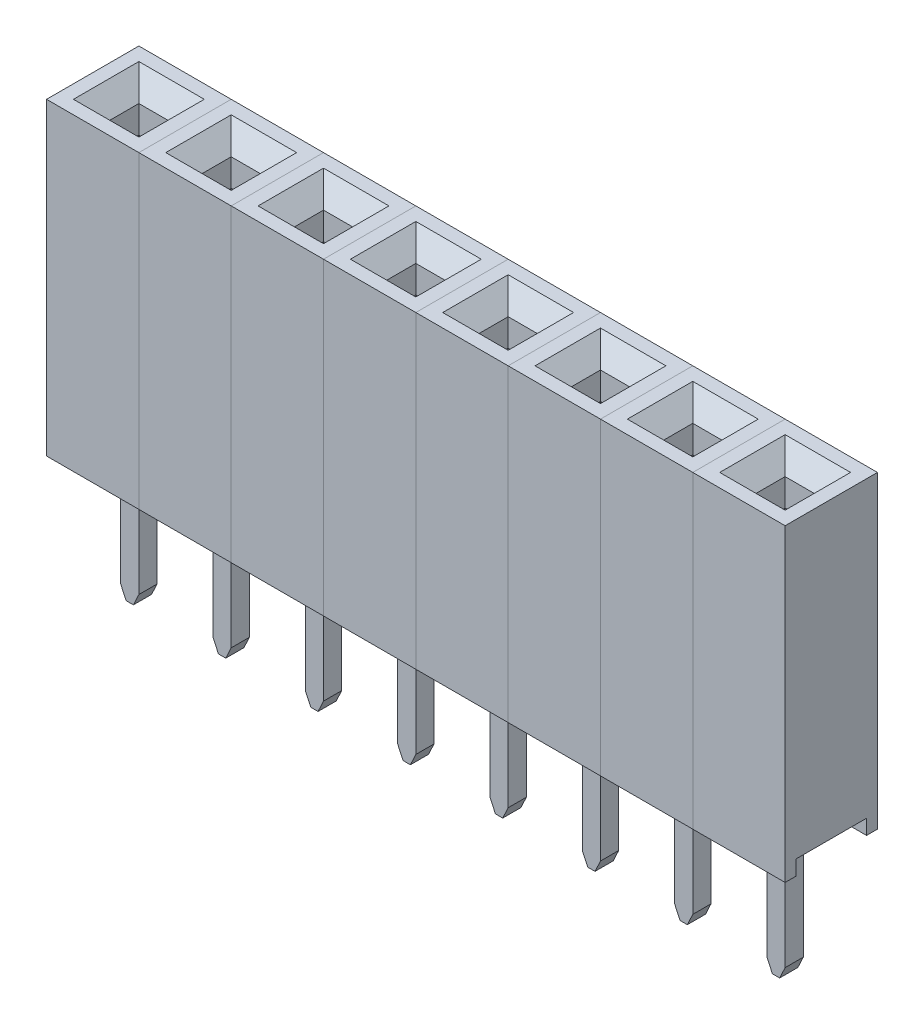
SolidWorks part; units mm, degrees
ref_plane "Front" through (0, 0, 0) normal (0, 0, 1) x (1, 0, 0)
ref_plane "Top" through (0, 0, 0) normal (0, 1, 0) x (1, 0, 0)
ref_plane "Right" through (0, 0, 0) normal (1, 0, 0) x (0, 0, -1)
sketch "Sketch1" plane through (0, 0, 0) normal (0, 0, 1) x (1, 0, 0)
  line L1 (1.27, -4.25) -> (-1.27, -4.25)
  line L2 (1.27, -4.25) -> (1.27, 4.25)
  line L3 (1.27, 4.25) -> (-1.27, 4.25)
  line L4 (-1.27, -4.25) -> (-1.27, 4.25)
  line L5 (1.27, -4.25) -> (-1.27, 4.25) construction
  line L6 (1.27, 4.25) -> (-1.27, -4.25) construction
  point P0 (0, 0)
  dimension "D1" = 2.54
  dimension "D2" = 8.5
extrude "Boss-Extrude1" add sketch "Sketch1" along normal mid plane 2.54
sketch "Sketch2" plane through (0, 0, 0) normal (1, 0, 0) x (0, 0, -1)
  line L0 (-0.97, -4.25) -> (0.97, -4.25)
  line L1 (-1.27, -4.25) -> (1.27, -4.25) construction
  line L2 (0.97, -4.25) -> (0.97, -3.8396)
  line L3 (0.97, -3.8396) -> (-0.97, -3.8396)
  line L4 (-0.97, -3.8396) -> (-0.97, -4.25)
  line L5 (1.27, -4.25) -> (1.27, 4.25) construction
  line L6 (-1.27, -4.25) -> (-1.27, 4.25) construction
  dimension "D1" = 0.3
  dimension "D2" = 0.3
extrude "Cut-Extrude1" cut sketch "Sketch2" against normal mid plane 100
sketch "Sketch4" plane through (0, 4.25, 0) normal (0, 1, 0) x (1, 0, 0)
  line L0 (-1.27, 0) -> (1.27, 0) construction
  line L1 (-1.27, -1.27) -> (-1.27, 1.27) construction
  line L2 (1.27, -1.27) -> (1.27, 1.27) construction
  line L4 (-0.875, 0.875) -> (0.875, 0.875)
  line L5 (-0.875, 0.875) -> (-0.875, -0.875)
  line L6 (-0.875, -0.875) -> (0.875, -0.875)
  line L7 (0.875, 0.875) -> (0.875, -0.875)
  line L8 (-0.875, 0.875) -> (0.875, -0.875) construction
  line L9 (-0.875, -0.875) -> (0.875, 0.875) construction
  line L10 (-0.4, 0.4) -> (0.4, 0.4)
  line L11 (-0.4, 0.4) -> (-0.4, -0.4)
  line L12 (-0.4, -0.4) -> (0.4, -0.4)
  line L13 (0.4, 0.4) -> (0.4, -0.4)
  line L14 (-0.4, 0.4) -> (0.4, -0.4) construction
  line L15 (-0.4, -0.4) -> (0.4, 0.4) construction
  point P6 (0, 0)
  point P11 (0, 0)
  point P16 (0, 0)
  dimension "D1" = 1.75
  dimension "D2" = 0.8
extrude "Cut-Extrude2" cut sketch "Sketch4" against normal blind 1.5 contours L13 L10 L11 L12 region at (0, 4.25, 0)
chamfer "Chamfer1" distance 0.5 angle 45 4 edges at (0, 4.25, -0.4) (-0.4, 4.25, 0) (0, 4.25, 0.4) (0.4, 4.25, 0)
sketch "Sketch5" plane through (0, 0, 0) normal (0, 1, 0) x (1, 0, 0)
  line L1 (-0.9, 0.9) -> (0.9, 0.9)
  line L2 (-0.9, 0.9) -> (-0.9, -0.9)
  line L3 (-0.9, -0.9) -> (0.9, -0.9)
  line L4 (0.9, 0.9) -> (0.9, -0.9)
extrude "Cut-Extrude3" cut sketch "Sketch5" against normal blind 3 and the other way blind 3
sketch "Sketch9" plane through (0, 0, 0) normal (0, 0, 1) x (1, 0, 0)
  line L0 (0, 1.6008) -> (0, -6.2684) construction
  line L1 (0.8528, -1.3416) -> (0.6022, -1.2609)
  line L2 (0.6022, -1.2609) -> (0.4133, 1.4919)
  line L3 (0.2803, 1.3393) -> (0.5075, -1.9717)
  line L4 (0.8528, -1.3416) -> (0.8528, -2.6933)
  line L5 (0.8528, -2.6933) -> (0.2807, -3.0533)
  line L6 (0.2807, -3.0533) -> (-0.2807, -3.0533)
  line L7 (-0.8528, -2.6933) -> (-0.2807, -3.0533)
  line L8 (-0.8528, -1.3416) -> (-0.8528, -2.6933)
  line L9 (-0.8528, -1.3416) -> (-0.6022, -1.2609)
  line L10 (-0.6022, -1.2609) -> (-0.4133, 1.4919)
  line L11 (-0.2803, 1.3393) -> (-0.5075, -1.9717)
  line L12 (-0.1, -7.6212) -> (0.1, -7.6212)
  line L13 (0.1, -7.6212) -> (0.25, -7.2995)
  line L14 (0.25, -7.2995) -> (0.25, -3.0533)
  line L15 (-0.1, -7.6212) -> (-0.25, -7.2995)
  line L16 (-0.25, -7.2995) -> (-0.25, -3.0533)
  line L19 (0, 0) -> (0, -10.2857) construction
  arc A0 (0.4133, 1.4919) -> (0.2803, 1.3393) centre (0.2705, 1.4821) ccw
  arc A1 (0.5075, -1.9717) -> (0, -2.3943) centre (0.101, -1.9996) cw
  arc A2 (-0.5075, -1.9717) -> (0, -2.3943) centre (-0.101, -1.9996) ccw
  arc A3 (-0.4133, 1.4919) -> (-0.2803, 1.3393) centre (-0.2705, 1.4821) cw
  point P16 (0, -3.0533)
  point P24 (-0.25, -4.3212)
  dimension "D1" = 115
  dimension "D2" = 115
  dimension "D3" = 0.25
  dimension "D4" = 0.2
  dimension "D5" = 0.25
  dimension "D6" = 3.3
extrude "Boss-Extrude4" add sketch "Sketch9" along normal mid plane 1.7 contours A1 L0 L6 L5 L4 L1 L2 A0 L3 | L0 A2 L11 A3 L10 L9 L8 L7 L6 region at (0.478, -1.4346, 0) region at (-0.478, -1.4346, 0)
extrude "Boss-Extrude5" add sketch "Sketch9<3>" along normal mid plane 0.5 contours L16 L15 L12 L13 L14 L6 region at (0, -5.2903, 0)
sketch "Sketch9<3>" plane through (0, 0, 0) normal (0, 0, 1) x (1, 0, 0) same geometry as "Sketch9"
pattern_linear "LPattern1" count 8 spacing 2.54 along (1, 0, 0) of bodies 108
